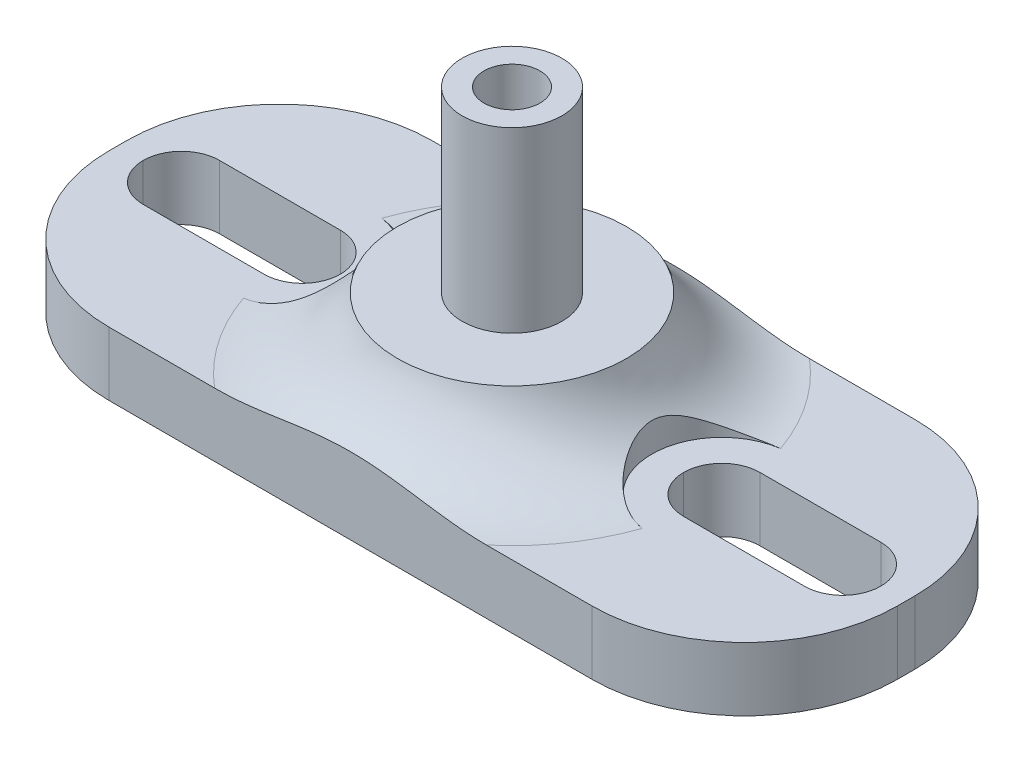
SolidWorks part; units mm, degrees
ref_plane "Front Plane" through (0, 0, 0) normal (0, 0, 1) x (1, 0, 0)
ref_plane "Top Plane" through (0, 0, 0) normal (0, 1, 0) x (1, 0, 0)
ref_plane "Right Plane" through (0, 0, 0) normal (1, 0, 0) x (0, 0, -1)
sketch "Sketch1" plane through (0, 0, 0) normal (0, 1, 0) x (1, 0, 0)
  line L0 (0, 0) -> (-31, 0) construction
  line L1 (-31, -12.7) -> (31, -12.7)
  line L2 (-31, -12.7) -> (-31, 12.7)
  line L3 (-31, 12.7) -> (31, 12.7)
  line L4 (31, -12.7) -> (31, 12.7)
  line L5 (-31, -12.7) -> (31, 12.7) construction
  line L6 (-31, 12.7) -> (31, -12.7) construction
  line L7 (0, 0) -> (0, 9.5595) construction
  line L8 (29, 3) -> (13.5, -3) construction
  line L9 (-29, -3) -> (-13.5, -3)
  line L10 (-29, -3) -> (-29, 3)
  line L11 (-29, 3) -> (-13.5, 3)
  line L12 (-13.5, -3) -> (-13.5, 3)
  line L13 (-29, -3) -> (-13.5, 3) construction
  line L14 (-29, 3) -> (-13.5, -3) construction
  line L15 (29, -3) -> (13.5, 3) construction
  line L16 (13.5, -3) -> (13.5, 3)
  line L17 (29, 3) -> (13.5, 3)
  line L18 (29, -3) -> (29, 3)
  line L19 (29, -3) -> (13.5, -3)
  circle A0 centre (0, 0) radius 3.925
  circle A1 centre (0, 0) radius 2.2
  point P0 (0, 0)
  point P11 (-21.25, 0)
  point P20 (21.25, 0)
  dimension "D1" = 7.85
  dimension "D2" = 4.4
  dimension "D3" = 13.5
  dimension "D4" = 25.4
  dimension "D5" = 62
  dimension "D6" = 2
  dimension "D7" = 6
extrude "Boss-Extrude1" add sketch "Sketch1" along normal blind 5 contours L1 L4 L3 L2 A0 L12 L9 L10 L11 L18 L19 L16 L17 region at (-30.33, 0, 0)
extrude "Boss-Extrude2" add sketch "Sketch1<3>" along normal blind 24.5 contours A0 A1 region at (-3.814, 0, 0)
sketch "Sketch1<3>" plane through (0, 0, 0) normal (0, 1, 0) x (1, 0, 0) same geometry as "Sketch1"
fillet "Fillet1" radius 3 8 edges at (29, 2.5, 3) (13.5, 2.5, 3) (29, 2.5, -3) (13.5, 2.5, -3) (-29, 2.5, 3) (-29, 2.5, -3) (-13.5, 2.5, 3) (-13.5, 2.5, -3)
sketch "Sketch2" plane through (0, 5, 0) normal (0, 1, 0) x (1, 0, 0)
  circle A0 centre (0, 0) radius 9
  dimension "D1" = 18
extrude "Boss-Extrude3" add sketch "Sketch2" along normal blind 5.5
sketch "Sketch3" plane through (0, 5, 0) normal (0, 1, 0) x (1, 0, 0)
  line L0 (0, 0) -> (0, -9.5283) construction
  line L1 (-11.656, 0) -> (13.344, 0) construction
  circle A0 centre (16.5, 0) radius 5.5
  circle A1 centre (-16.5, 0) radius 5.5
  circle A2 centre (0, 0) radius 11 construction
  dimension "D1" = 11
fillet "Fillet2" radius 8 1 edges at (0, 5, 9)
extrude "Cut-Extrude1" cut sketch "Sketch3" along normal blind 5.5
fillet "Fillet3" radius 12 4 edges at (31, 2.5, 12.7) (31, 2.5, -12.7) (-31, 2.5, -12.7) (-31, 2.5, 12.7)
sketch "Sketch4" plane through (0, 24.5, 0) normal (0, 1, 0) x (1, 0, 0)
  circle A0 centre (0, 0) radius 2.2
extrude "Cut-Extrude2" cut sketch "Sketch4" against normal through all
